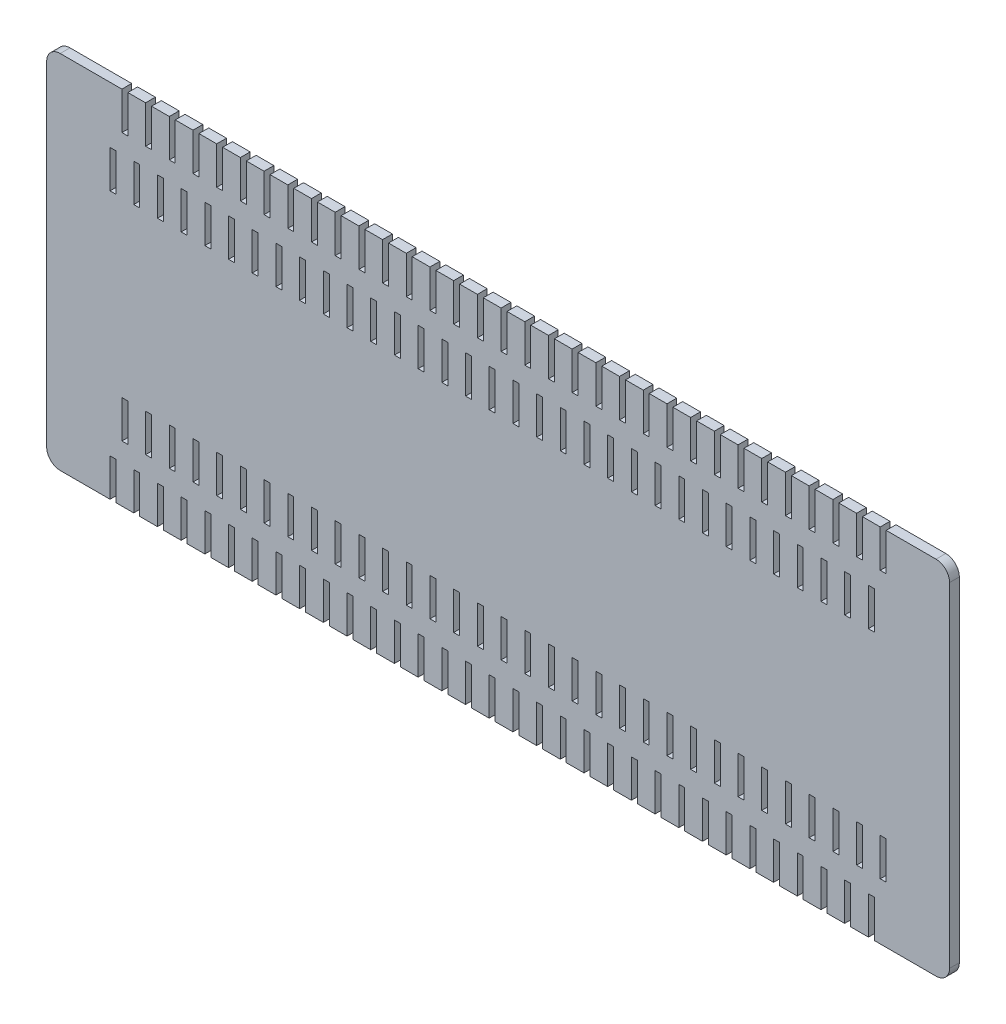
SolidWorks part; units mm, degrees
ref_plane "Front Plane" through (0, 0, 0) normal (0, 0, 1) x (1, 0, 0)
ref_plane "Top Plane" through (0, 0, 0) normal (0, 1, 0) x (1, 0, 0)
ref_plane "Right Plane" through (0, 0, 0) normal (1, 0, 0) x (0, 0, -1)
sketch "Sketch1" plane through (0, 0, 0) normal (0, 0, 1) x (1, 0, 0)
  line L4 (76.2, -28.194) -> (76.2, 28.194) construction
  line L6 (73.914, 30.48) -> (-73.914, 30.48) construction
  line L7 (-73.914, -30.48) -> (73.914, -30.48) construction
  line L8 (-76.2, 28.194) -> (-76.2, -28.194) construction
  line L13 (76.2, -28.194) -> (76.2, 28.194)
  line L14 (73.914, 30.48) -> (-73.914, 30.48)
  line L15 (-73.914, -30.48) -> (73.914, -30.48)
  line L16 (-76.2, 28.194) -> (-76.2, -28.194)
  arc A4 (73.914, -30.48) -> (76.2, -28.194) centre (73.914, -28.194) ccw construction
  arc A5 (76.2, 28.194) -> (73.914, 30.48) centre (73.914, 28.194) ccw construction
  arc A6 (-73.914, 30.48) -> (-76.2, 28.194) centre (-73.914, 28.194) ccw construction
  arc A7 (-76.2, -28.194) -> (-73.914, -30.48) centre (-73.914, -28.194) ccw construction
  arc A12 (73.914, -30.48) -> (76.2, -28.194) centre (73.914, -28.194) ccw
  arc A13 (76.2, 28.194) -> (73.914, 30.48) centre (73.914, 28.194) ccw
  arc A14 (-73.914, 30.48) -> (-76.2, 28.194) centre (-73.914, 28.194) ccw
  arc A15 (-76.2, -28.194) -> (-73.914, -30.48) centre (-73.914, -28.194) ccw
extrude "Boss-Extrude1" add sketch "Sketch1" along normal blind 1.651
sketch "Sketch4" plane through (0, 0, 1.651) normal (0, 0, 1) x (1, 0, 0)
  line L0 (-76.2, 27.305) -> (76.2, 27.305) construction
  line L1 (-76.2, 28.194) -> (-76.2, -28.194) construction
  line L2 (76.2, -28.194) -> (76.2, 28.194) construction
  line L3 (73.914, 30.48) -> (-73.914, 30.48) construction
  line L4 (222.25, -9.906) -> (222.25, 9.906) construction
  line L5 (-63.5, 24.13) -> (-62.5, 24.13)
  line L6 (-63.5, 24.13) -> (-63.5, 30.48)
  line L7 (-63.5, 30.48) -> (-62.5, 30.48)
  line L8 (-62.5, 24.13) -> (-62.5, 30.48)
  line L9 (-63.5, 24.13) -> (-62.5, 30.48) construction
  line L10 (-63.5, 30.48) -> (-62.5, 24.13) construction
  line L11 (222.25, -9.906) -> (222.25, 9.906)
  line L12 (222.25, 0) -> (-284.6386, 0) construction
  line L13 (63, -17.78) -> (-61.9587, -17.78) construction
  line L14 (-61.9587, -17.78) -> (-61.9587, 27.305) construction
  line L19 (-61.9587, 4.7625) -> (21.2556, 4.7625) construction
  line L20 (-63.5, -20.955) -> (-62.5, -14.605) construction
  line L21 (-63.5, -14.605) -> (-62.5, -20.955) construction
  line L22 (-62.5, -14.605) -> (-62.5, -20.955)
  line L23 (-63.5, -20.955) -> (-62.5, -20.955)
  line L24 (-63.5, -14.605) -> (-63.5, -20.955)
  line L25 (-63.5, -14.605) -> (-62.5, -14.605)
  arc A1 (-63, 30.48) -> (-63, 24.13) centre (-63, 27.305) ccw construction
  arc A5 (-63, -24.13) -> (-63, -30.48) centre (-63, -27.305) ccw construction
  arc A6 (63, 14.605) -> (63, 20.955) centre (63, 17.78) ccw construction
  arc A7 (63, -20.955) -> (63, -14.605) centre (63, -17.78) ccw construction
  point P8 (-63, 27.305)
  point P28 (-63, 30.48)
  point P41 (-63, -17.78)
  dimension "D1" = 3.175
  dimension "D3" = 1
extrude "Cut-Extrude1" cut sketch "Sketch4" against normal through all
pattern_linear "LPattern1" count 33 spacing 4 along (1, 0, 0) of "Cut-Extrude1"
sketch "Sketch5" plane through (0, 0, -17.6784) normal (1, 0, 0) x (0, 1, 0)
  line L0 (0, 0) -> (0, 44.6864)
pattern_circular "CirPattern1" count 2 over 180 of "LPattern1", "Cut-Extrude1"
sketch "Sketch6" plane through (0, 0, 1.651) normal (0, 0, 1) x (1, 0, 0)
  line L0 (-63.5, 24.13) -> (-63.5, 24.1696)
  line L1 (-63.5, 24.13) -> (-63.5, 30.48) construction
  line L2 (-63.5, 24.13) -> (-63, 24.13)
  line L3 (63, 20.955) -> (63.5, 20.955)
  line L4 (63.5, 20.955) -> (63.5, 20.9154)
  line L5 (63.5, 14.605) -> (63.5, 14.6446)
  line L6 (63.5, 14.605) -> (63.5, 20.955) construction
  line L7 (63.5, 14.605) -> (63, 14.605)
  line L8 (65.5, -14.605) -> (65.5, -15.8228)
  line L9 (65.5, -14.605) -> (65.5, -20.955) construction
  line L10 (65.5, -14.605) -> (64.5, -14.605)
  line L11 (64.5, -14.605) -> (64.5, -14.9817)
  line L12 (64.5, -20.955) -> (64.5, -20.5783)
  line L13 (64.5, -14.605) -> (64.5, -20.955) construction
  line L14 (64.5, -20.955) -> (65.5, -20.955)
  line L15 (65.5, -20.955) -> (65.5, -19.7372)
  line L16 (-64.5, -24.5067) -> (-64.5, -24.13)
  line L17 (-64.5, -24.13) -> (-64.5, -30.48) construction
  line L18 (-64.5, -24.13) -> (-65.5, -24.13)
  line L19 (-65.5, -24.13) -> (-65.5, -25.3478)
  line L20 (-65.5, -24.13) -> (-65.5, -30.48) construction
  line L21 (-65.5, -29.2622) -> (-65.5, -30.48)
  line L22 (-65.5, -30.48) -> (-64.5, -30.48)
  line L23 (-64.5, -30.48) -> (-64.5, -30.1033)
  line L24 (-63.5, 30.4404) -> (-63.5, 30.48)
  line L25 (73.914, 30.48) -> (-73.914, 30.48) construction
  line L26 (-63.5, 30.48) -> (-63, 30.48)
  arc A0 (-63, 30.48) -> (-63, 24.13) centre (-63, 27.305) ccw construction
  arc A1 (-63.5, 24.1696) -> (-63, 24.13) centre (-63, 27.305) ccw
  arc A2 (-63, 30.48) -> (-63.5, 30.4404) centre (-63, 27.305) ccw
  arc A3 (-63, -24.13) -> (-63, -30.48) centre (-63, -27.305) ccw construction
  arc A4 (63, -20.955) -> (63, -14.605) centre (63, -17.78) ccw construction
  arc A5 (63, 14.605) -> (63, 20.955) centre (63, 17.78) ccw construction
  arc A6 (-64.5, -24.5067) -> (-65.5, -25.3478) centre (-63, -27.305) ccw
  arc A7 (64.5, -20.5783) -> (65.5, -19.7372) centre (63, -17.78) ccw
  arc A8 (63, 14.605) -> (63.5, 14.6446) centre (63, 17.78) ccw
  arc A9 (-65.5, -29.2622) -> (-64.5, -30.1033) centre (-63, -27.305) ccw
  arc A10 (65.5, -15.8228) -> (64.5, -14.9817) centre (63, -17.78) ccw
  arc A11 (63.5, 20.9154) -> (63, 20.955) centre (63, 17.78) ccw
  arc A12 (-63.5, 24.1696) -> (-63, 24.13) centre (-63, 27.305) ccw
